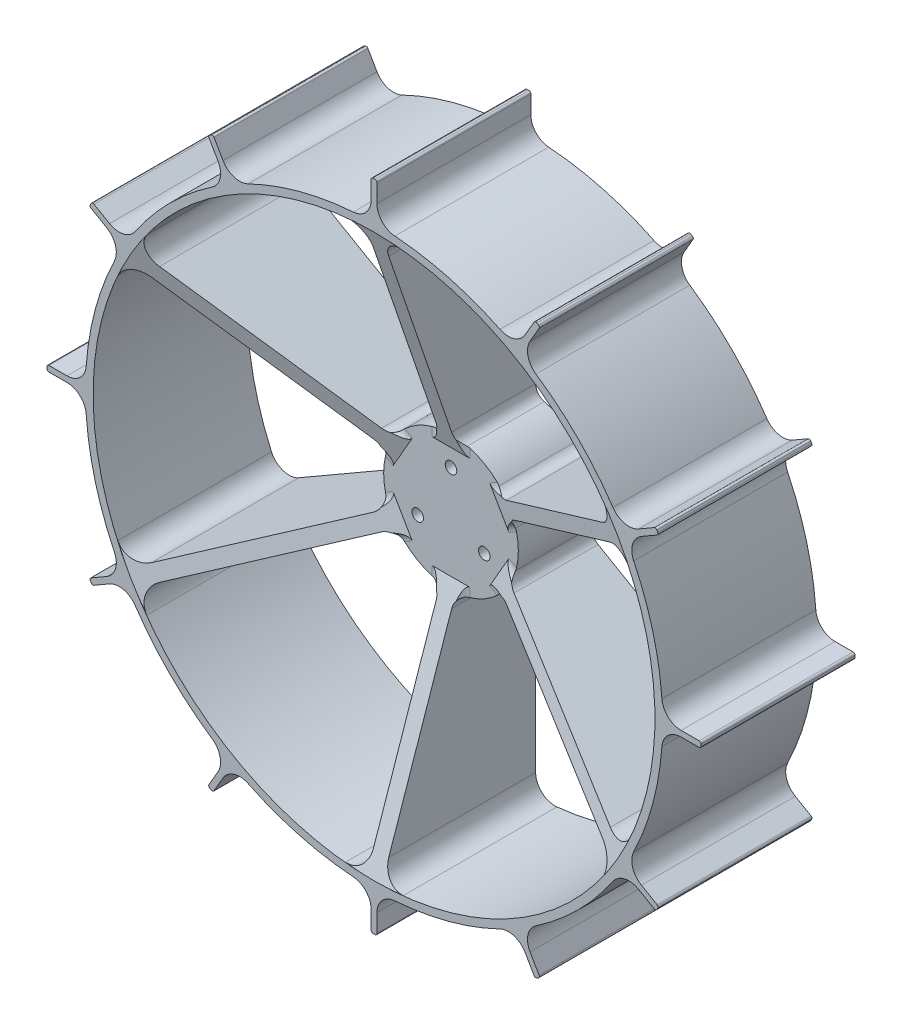
SolidWorks part; units mm, degrees
ref_plane "Front Plane" through (0, 0, 0) normal (0, 0, 1) x (1, 0, 0)
ref_plane "Top Plane" through (0, 0, 0) normal (0, 1, 0) x (1, 0, 0)
ref_plane "Right Plane" through (0, 0, 0) normal (1, 0, 0) x (0, 0, -1)
sketch "Sketch1" plane through (0, 0, 0) normal (0, 0, 1) x (1, 0, 0)
  circle A0 centre (0, 0) radius 75
  circle A1 centre (0, 0) radius 73
  dimension "D1" = 150
  dimension "D2" = 2
extrude "Boss-Extrude1" add sketch "Sketch1" along normal blind 40
sketch "Sketch2" plane through (0, 0, 0) normal (0, 0, 1) x (1, 0, 0)
  line L0 (0, 0) -> (0, 169.9925) construction
  line L1 (-0.75, 84.9962) -> (0.75, 84.9962)
  line L2 (0.75, 84.9962) -> (0.75, 74.9962)
  line L3 (-0.75, 84.9962) -> (-0.75, 74.9962)
  circle A0 centre (0, 0) radius 75 construction
  circle A1 centre (0, 0) radius 75
  point P6 (0, 84.9962)
  dimension "D1" = 1.5
  dimension "D2" = 10
extrude "Boss-Extrude2" add sketch "Sketch2" along normal up to surface (40 mm away) contours A1 L0 L1 L3 | L0 A1 L2 L1 region at (-0.375, 79.9975, 0) region at (0.375, 79.9975, 0) up to face at (75, 0, 40)
fillet "Fillet1" radius 5 2 edges at (-0.75, 74.9962, 20) (0.75, 74.9962, 20)
fillet "Fillet2" radius 0.5 2 edges at (-0.75, 84.9962, 20) (0.75, 84.9962, 20)
pattern_circular "CirPattern1" count 12 over 360 about axis through (0, 0, 40) along (0, 0, -1) of "Boss-Extrude2", "Fillet1", "Fillet2"
sketch "Sketch3" plane through (0, 0, 0) normal (0, 0, 1) x (1, 0, 0)
  circle A0 centre (0, 0) radius 17.5
  dimension "D1" = 35
extrude "Boss-Extrude3" add sketch "Sketch3" along normal offset from surface (20 mm away) 20 separate body up to face at (0, 0, 40)
sketch "Sketch4" plane through (0, 0, 20) normal (0, 0, 1) x (1, 0, 0)
  line L0 (0, 0) -> (-8.6603, -5) construction
  line L1 (0, 0) -> (8.6603, -5) construction
  line L2 (0, 0) -> (0, 10) construction
  circle A0 centre (0, 10) radius 1.5
  circle A1 centre (-8.6603, -5) radius 1.5
  circle A2 centre (8.6603, -5) radius 1.5
  dimension "D3" = 3
  dimension "D1" = 120
  dimension "D2" = 120
  dimension "D4" = 10
extrude "Cut-Extrude1" cut sketch "Sketch4" against normal through all both and the other way through all
sketch "Sketch5" plane through (0, 0, 0) normal (1, 0, 0) x (0, 0, -1)
  line L0 (0, -73) -> (-40, -73)
  line L1 (-40, 73) -> (0, 73)
  line L2 (-40, 73) -> (0, 73)
  line L3 (0, -73) -> (-40, -73)
  line L4 (0, -17.5) -> (-20, -17.5)
  line L5 (-20, 17.5) -> (0, 17.5)
  line L7 (0, -17.5) -> (-20, -17.5)
  line L8 (-40, 73) -> (-20, 14.5)
  line L9 (0, 17.5) -> (0, 73)
  line L14 (-20, 14.5) -> (0, 14.5)
  line L15 (0, 17.5) -> (0, 14.5)
  dimension "D1" = 3
extrude "Boss-Extrude4" add sketch "Sketch5" along normal mid plane 4 contours L9 L2 L8 region at (0, 47, 15.5556)
fillet "Fillet3" radius 5 2 edges at (-2, 72.9726, 19.9953) (2, 72.9726, 19.9953)
fillet "Fillet4" radius 3 4 edges at (-2, 15.9427, 20) (2, 15.9427, 20) (-2, 17.3853, 10) (2, 17.3853, 10)
pattern_circular "CirPattern2" count 6 over 360 about axis through (0, 0, 89.4975) along (0, 0, -1) of "Boss-Extrude4", "Fillet3", "Fillet4"
